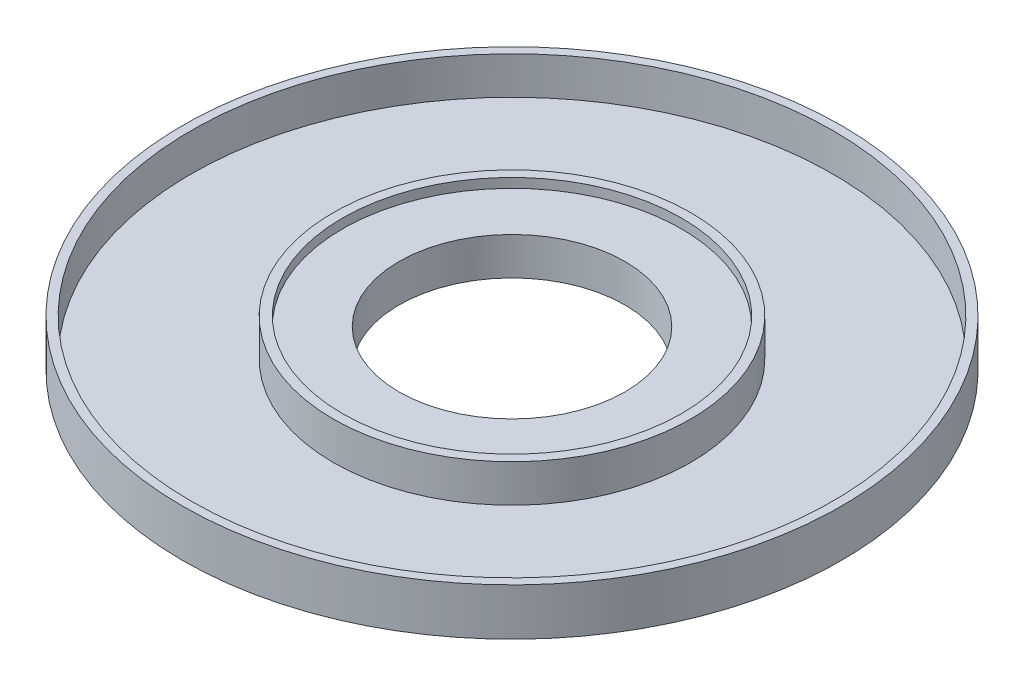
SolidWorks part; units mm, degrees
ref_plane "Front Plane" through (0, 0, 0) normal (0, 0, 1) x (1, 0, 0)
ref_plane "Top Plane" through (0, 0, 0) normal (0, 1, 0) x (1, 0, 0)
ref_plane "Right Plane" through (0, 0, 0) normal (1, 0, 0) x (0, 0, -1)
sketch "Sketch1" plane through (0, 0, 0) normal (0, 1, 0) x (1, 0, 0)
  circle A0 centre (0, 0) radius 1750
extrude "Boss-Extrude1" add sketch "Sketch1" along normal blind 500
sketch "Sketch2" plane through (0, 500, 0) normal (0, 1, 0) x (1, 0, 0)
  circle A0 centre (0, 0) radius 900
extrude "Cut-Extrude2" cut sketch "Sketch2" against normal blind 300
sketch "Sketch3" plane through (0, 0, 0) normal (0, -1, 0) x (1, 0, 0)
  circle A0 centre (0, 0) radius 600
extrude "Cut-Extrude3" cut sketch "Sketch3" against normal blind 300
sketch "Sketch4" plane through (0, 500, 0) normal (0, 1, 0) x (1, 0, 0)
  circle A0 centre (0, 0) radius 1704.2196
  circle A1 centre (0, 0) radius 949.3021
extrude "Cut-Extrude4" cut sketch "Sketch4" against normal blind 450
sketch "Sketch6" plane through (0, 0, 0) normal (1, 0, 0) x (0, 0, -1)
  line L0 (0, 0) -> (0, 250)
  line L1 (0, 250) -> (1750, 250)
  line L2 (1750, 0) -> (1750, 500) construction
  line L3 (1750, 250) -> (1750, 0)
  line L4 (1750, 0) -> (-1750, 0)
  line L5 (-1750, 0) -> (-1750, 250)
  line L6 (-1750, 500) -> (-1750, 0) construction
  line L7 (-1750, 250) -> (0, 250)
  line L8 (1750, 250) -> (1750, 500)
  line L9 (1750, 500) -> (-1750, 500)
  line L10 (-1750, 500) -> (-1750, 250)
extrude "Cut-Extrude5" cut sketch "Sketch6" against normal through all both and the other way through all contours L9 L10 L7 L1 L8 region at (0, 375, 0)
